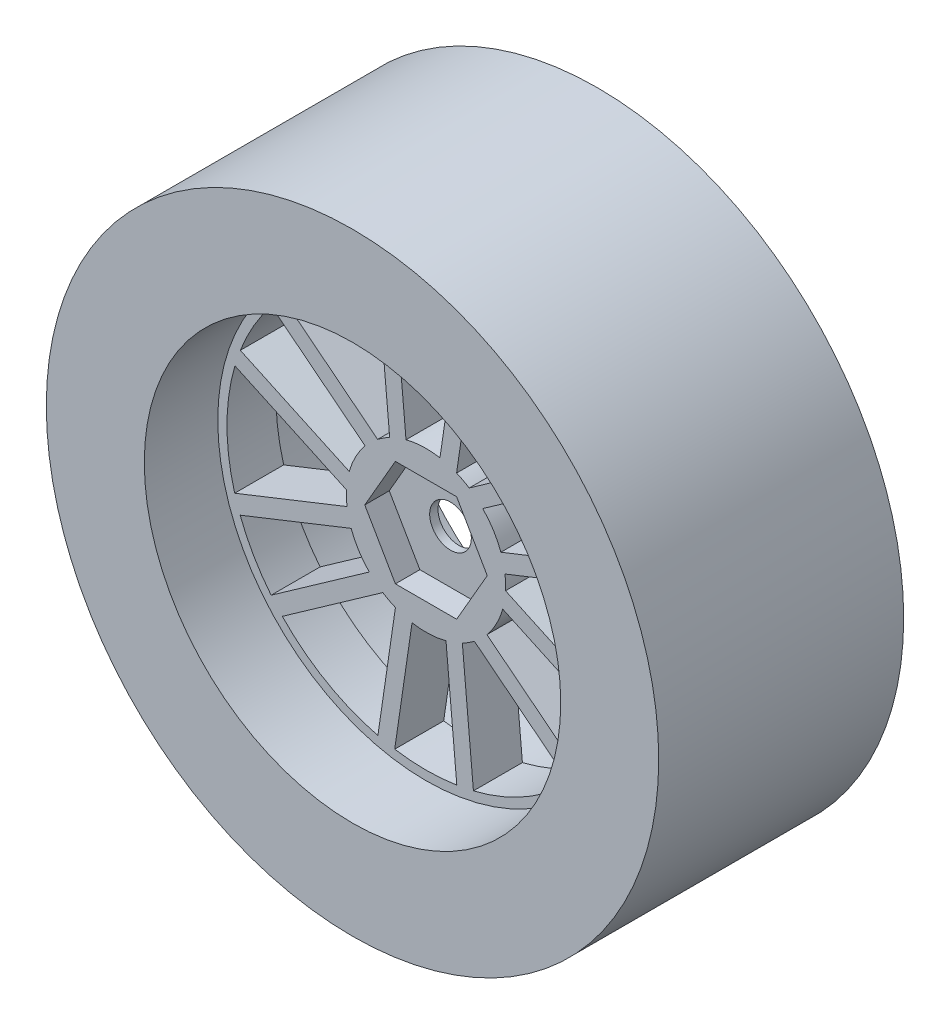
SolidWorks part; units mm, degrees
ref_plane "Front Plane" through (0, 0, 0) normal (0, 0, 1) x (1, 0, 0)
ref_plane "Top Plane" through (0, 0, 0) normal (0, 1, 0) x (1, 0, 0)
ref_plane "Right Plane" through (0, 0, 0) normal (1, 0, 0) x (0, 0, -1)
sketch "Sketch1" plane through (0, 0, 0) normal (0, 0, 1) x (1, 0, 0)
  circle A0 centre (0, 0) radius 31.75
  dimension "D1" = 63.5
extrude "Boss-Extrude1" add sketch "Sketch1" along normal blind 25.4
sketch "Sketch3" plane through (0, 0, 25.4) normal (0, 0, 1) x (1, 0, 0)
  circle A2 centre (0, 0) radius 21.59
  circle A3 centre (0, 0) radius 21.59
  dimension "D1" = 10.16
extrude "Cut-Extrude1" cut sketch "Sketch3" against normal blind 7.62
sketch "Sketch4" plane through (0, 0, 0) normal (0, 0, -1) x (-1, 0, 0)
  circle A2 centre (0, 0) radius 21.59
  circle A3 centre (0, 0) radius 21.59
  dimension "D1" = 10.16
extrude "Cut-Extrude2" cut sketch "Sketch4" against normal blind 12.7
sketch "Sketch5" plane through (0, 0, 12.7) normal (0, 0, -1) x (-1, 0, 0)
  line L0 (-4.9903, 20.0251) -> (-3.1698, 7.6222)
  line L1 (-3.2455, 20.3807) -> (-1.4469, 8.1272)
  line L2 (-3.2627, 8.255) -> (3.8493, 8.255) construction
  line L3 (2.073, 7.9905) -> (3.1944, 20.3888)
  line L4 (3.7671, 7.3454) -> (4.9156, 20.0435)
  line L5 (2.6337, 14.1896) -> (4.3414, 13.6944) construction
  line L6 (-4.9903, 20.0251) -> (4.9156, 20.0435) construction
  circle A0 centre (0, 0) radius 8.255
  circle A1 centre (0, 0) radius 20.6375
  dimension "D1" = 16.51
  dimension "D2" = 41.275
  dimension "D4" = 1.778
  dimension "D3" = 1.778
  dimension "D5" = 9.906
  dimension "D6" = 7.112
extrude "Cut-Extrude3" cut sketch "Sketch5" against normal through all contours L0 A1 L4 A0 | L1 A1 L0 A0 | L3 A1 L1 A0 | L4 A1 L3 A0 region at (3.2182, 14.061, 12.7) region at (4.6534, 13.7395, 12.7) region at (-0.1292, 14.9725, 12.7) region at (-3.493, 13.9645, 12.7)
extrude "Boss-Extrude2" add sketch "Sketch5<3>" against normal up to surface (5.08 mm away) contours L1 A1 L0 A0 | L4 A1 L3 A0 region at (3.2182, 14.061, 12.7) region at (-3.493, 13.9645, 12.7) up to face at (20.6375, 0, 17.78)
sketch "Sketch5<3>" plane through (0, 0, 12.7) normal (0, 0, -1) x (-1, 0, 0) same geometry as "Sketch5"
pattern_circular "CirPattern1" count 6 over 360 about axis through (0, 0, 25.4) along (0, 0, -1) of "Boss-Extrude2"
sketch "Sketch7" plane through (0, 0, 17.78) normal (0, 0, 1) x (1, 0, 0)
  line L1 (6.35, 0) -> (3.175, 5.4993)
  line L2 (3.175, 5.4993) -> (-3.175, 5.4993)
  line L3 (-3.175, 5.4993) -> (-6.35, 0)
  line L4 (-6.35, 0) -> (-3.175, -5.4993)
  line L5 (-3.175, -5.4993) -> (3.175, -5.4993)
  line L6 (3.175, -5.4993) -> (6.35, 0)
  circle A0 centre (0, 0) radius 5.4993 construction
  dimension "D1" = 12.7
extrude "Cut-Extrude5" cut sketch "Sketch7" against normal blind 2.54
sketch "Sketch8" plane through (0, 0, 15.24) normal (0, 0, 1) x (1, 0, 0)
  circle A0 centre (0, 0) radius 2.159
  dimension "D1" = 4.318
extrude "Cut-Extrude6" cut sketch "Sketch8" against normal blind 2.54
sketch "Sketch9" plane through (0, 0, 12.7) normal (0, 0, -1) x (-1, 0, 0)
  line L1 (7.0204, 0) -> (2.1694, 6.6768)
  line L2 (2.1694, 6.6768) -> (-5.6796, 4.1265)
  line L3 (-5.6796, 4.1265) -> (-5.6796, -4.1265)
  line L4 (-5.6796, -4.1265) -> (2.1694, -6.6768)
  line L5 (2.1694, -6.6768) -> (7.0204, 0)
  circle A1 centre (0, 0) radius 5.6796 construction
  dimension "D1" = 12.7
extrude "Cut-Extrude7" cut sketch "Sketch9" against normal blind 1.6764
